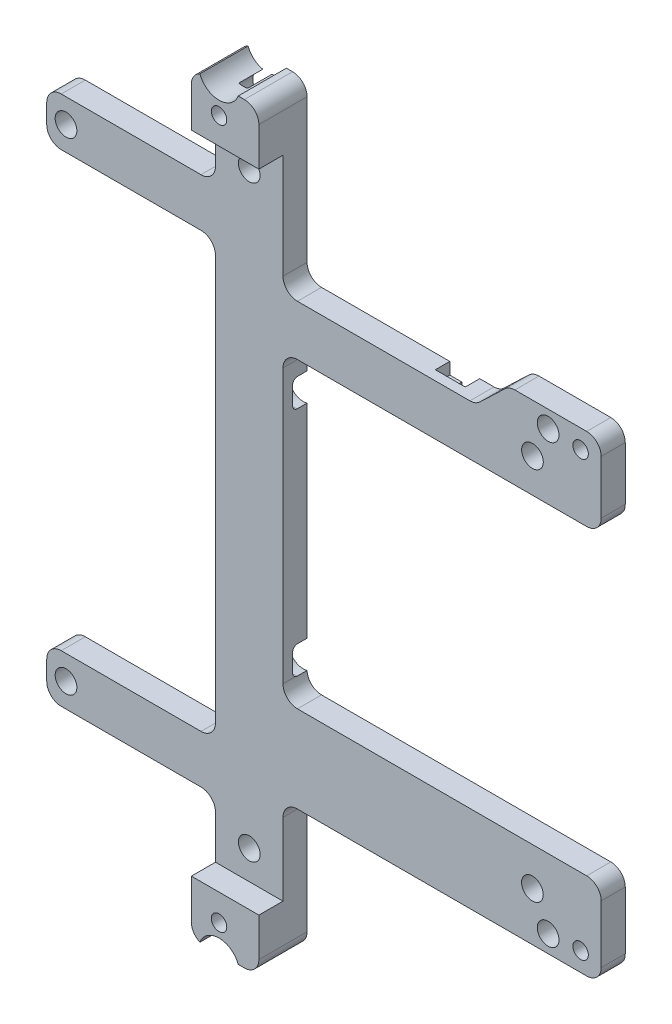
SolidWorks part; units mm, degrees
ref_plane "Front Plane" through (0, 0, 0) normal (1, 0, 0) x (0, 1, 0)
ref_plane "Top Plane" through (0, 0, 0) normal (0, 0, 1) x (0, 1, 0)
ref_plane "Right Plane" through (0, 0, 0) normal (0, 1, 0) x (-1, 0, 0)
sketch "Sketch1" plane through (0, 0, 0) normal (0, 0, 1) x (0, 1, 0)
  line L0 (-38.86, 0.005) -> (38.86, -0.005) construction
  line L1 (-38.86, 0.005) -> (38.86, -0.005) construction
  line L2 (0, 0) -> (0, 106.5364) construction
  line L13 (-67.5, 65.745) -> (67.5, 51.745) construction
  line L14 (-67.5, 51.745) -> (67.5, 65.745) construction
  line L17 (-45, 65.745) -> (45, 65.745)
  line L22 (62.0223, 59.9423) -> (59.9389, 57.5466) construction
  line L23 (62.1784, 57.7039) -> (59.7816, 59.7861) construction
  line L45 (42.2651, 11.7705) -> (42.2651, 52.7631) construction
  line L47 (-48.9476, 51.745) -> (-48.9476, -14.255)
  line L48 (-48.9476, -14.255) -> (-30.9476, -14.255)
  line L49 (-30.9476, -14.255) -> (-30.9476, 51.745)
  line L50 (-30.9476, 51.745) -> (31.792, 51.745)
  line L51 (31.792, 51.745) -> (31.792, -14.255)
  line L52 (31.792, -14.255) -> (48.8866, -14.255)
  line L53 (48.8866, -14.255) -> (48.8866, 4.8443)
  line L54 (48.8866, 4.8443) -> (42.2651, 11.7705)
  line L55 (42.2651, 11.7705) -> (42.2651, 51.745)
  line L60 (-55, 65.745) -> (-78, 65.745)
  line L62 (-78, 65.745) -> (-78, 51.745)
  line L63 (-78, 51.745) -> (-48.9476, 51.745)
  line L64 (78, 65.745) -> (78, 51.745)
  line L65 (55, 65.745) -> (78, 65.745)
  line L66 (78, 51.745) -> (42.2651, 51.745)
  line L67 (-55, 65.745) -> (-55, 100.745)
  line L68 (-55, 100.745) -> (-45, 100.745)
  line L69 (-45, 100.745) -> (-45, 65.745)
  line L70 (45, 100.745) -> (45, 65.745)
  line L71 (55, 100.745) -> (45, 100.745)
  line L72 (55, 65.745) -> (55, 100.745)
  circle A0 centre (-38.86, 0.005) radius 2.25
  circle A1 centre (38.86, -0.005) radius 2.25
  circle A2 centre (-60.99, 58.735) radius 2.25
  circle A3 centre (60.98, 58.745) radius 2.25
  circle A8 centre (-45, -9.995) radius 1.6
  circle A10 centre (45, -9.995) radius 1.6
  circle A14 centre (60.98, 58.745) radius 1.5874 construction
  circle A15 centre (-72.5, 60.005) radius 3
  circle A17 centre (72.5, 60.005) radius 3
  point P28 (0, 58.745)
  dimension "D1" = 4.5
  dimension "D4" = 4.5
  dimension "D5" = 4.5
  dimension "D10" = 4.5
  dimension "D11" = 3.2
  dimension "D13" = 45
  dimension "D12" = 10
  dimension "D14" = 6
  dimension "D16" = 70
  dimension "D2" = 77.72
  dimension "D3" = 0.01
  dimension "D6" = 22.13
  dimension "D7" = 58.73
  dimension "D8" = 99.84
  dimension "D9" = 58.74
  dimension "D15" = 72.5
  dimension "D17" = 14
  dimension "D18" = 23
  dimension "D19" = 10
  dimension "D20" = 35
  dimension "D22" = 66
  dimension "D23" = 18
  dimension "D24" = 62.7397
extrude "Boss-Extrude1" add sketch "Sketch1" along normal blind 5
sketch "Sketch4" plane through (0, 0, 5) normal (0, 0, 1) x (1, 0, 0)
  line L0 (-59.9423, 62.0223) -> (-57.5466, 59.9389) construction
  line L1 (-57.7039, 62.1784) -> (-59.7861, 59.7816) construction
  line L2 (-52.7631, 68.2675) -> (-66.1639, 68.2675) construction
  line L3 (-66.1639, 68.2675) -> (-66.1639, 50.4408) construction
  line L4 (-66.1639, 50.4408) -> (-106.6121, 50.4408) construction
  line L5 (-106.6121, 50.4408) -> (-106.6121, 34.0894) construction
  line L6 (-106.6121, 34.0894) -> (-66.1639, 34.0894) construction
  line L7 (-66.1639, 34.0894) -> (-66.1639, -39.7992) construction
  line L8 (-66.1639, -39.7992) -> (-105.8744, -39.7992) construction
  line L9 (-105.8744, -39.7992) -> (-105.8744, -55.1671) construction
  line L10 (-105.8744, -55.1671) -> (-65.4262, -55.1671) construction
  line L11 (-65.4262, -55.1671) -> (-65.4262, -83.2031) construction
  line L12 (-65.4262, -83.2031) -> (-51.2429, -83.2031) construction
  line L13 (-51.2429, -83.2031) -> (-51.2429, -48.9476) construction
  line L14 (-51.2429, -48.9476) -> (16.9144, -48.9476) construction
  line L15 (16.9144, -48.9476) -> (16.9144, -14.8647) construction
  line L16 (16.9144, -14.8647) -> (-49.6702, -14.8647) construction
  line L17 (-49.6702, -14.8647) -> (-49.6702, 30.0022) construction
  line L18 (-49.6702, 30.0022) -> (-49.6702, 31.792) construction
  line L19 (-49.6702, 31.792) -> (21.8605, 31.792) construction
  line L20 (21.8605, 31.792) -> (21.8605, 50.4408) construction
  line L21 (21.8605, 50.4408) -> (-3.2186, 50.4408) construction
  line L22 (-3.2186, 50.4408) -> (-11.7705, 42.2651) construction
  line L23 (-11.7705, 42.2651) -> (-52.7631, 42.2651) construction
  line L24 (-52.7631, 42.2651) -> (-52.7631, 68.2675) construction
  line L25 (-53.5293, 13.6559) -> (-53.5293, 8.5989) construction
  line L26 (-53.5293, 13.6559) -> (-57.5472, 13.6559) construction
  line L27 (-57.5472, 13.6559) -> (-57.5472, 8.5989) construction
  line L28 (-53.5293, 8.5989) -> (-57.5472, 8.5989) construction
  line L29 (-53.5293, 13.6559) -> (-57.5472, 8.5989) construction
  line L30 (-57.5472, 13.6559) -> (-53.5293, 8.5989) construction
  line L31 (-30.5241, 33.1453) -> (-30.5241, 30.4388) construction
  line L32 (-30.5241, 33.1453) -> (-34.3522, 33.1453) construction
  line L33 (-34.3522, 33.1453) -> (-34.3522, 30.4388) construction
  line L34 (-30.5241, 30.4388) -> (-34.3522, 30.4388) construction
  line L35 (-30.5241, 33.1453) -> (-34.3522, 30.4388) construction
  line L36 (-34.3522, 33.1453) -> (-30.5241, 30.4388) construction
  line L37 (-34.5262, 33.1453) -> (-34.5262, 30.4388) construction
  line L38 (-34.5262, 33.1453) -> (-37.7452, 33.1453) construction
  line L39 (-37.7452, 33.1453) -> (-37.7452, 30.4388) construction
  line L40 (-34.5262, 30.4388) -> (-37.7452, 30.4388) construction
  line L41 (-34.5262, 33.1453) -> (-37.7452, 30.4388) construction
  line L42 (-37.7452, 33.1453) -> (-34.5262, 30.4388) construction
  line L43 (-16.3911, 40.3217) -> (-16.3911, 37.7641) construction
  line L44 (-16.3911, 40.3217) -> (-19.6245, 40.3217) construction
  line L45 (-19.6245, 40.3217) -> (-19.6245, 37.7641) construction
  line L46 (-16.3911, 37.7641) -> (-19.6245, 37.7641) construction
  line L47 (-16.3911, 40.3217) -> (-19.6245, 37.7641) construction
  line L48 (-19.6245, 40.3217) -> (-16.3911, 37.7641) construction
  line L49 (-15.9373, 44.8094) -> (-15.9373, 40.9494) construction
  line L50 (-15.9373, 44.8094) -> (-22.1441, 44.8094) construction
  line L51 (-22.1441, 44.8094) -> (-22.1441, 40.9494) construction
  line L52 (-15.9373, 40.9494) -> (-22.1441, 40.9494) construction
  line L53 (-15.9373, 44.8094) -> (-22.1441, 40.9494) construction
  line L54 (-22.1441, 44.8094) -> (-15.9373, 40.9494) construction
  circle A0 centre (-58.745, 60.98) radius 1.5874 construction
  circle A1 centre (-52.5383, 22.8611) radius 3 construction
  circle A2 centre (-52.5383, -25.1544) radius 3 construction
  circle A3 centre (-10.615, -39.3884) radius 1 construction
  circle A4 centre (-10.615, -46.9884) radius 1 construction
  circle A5 centre (-19.6245, -25.1544) radius 3 construction
  circle A6 centre (-58.745, 60.98) radius 2.25 construction
  point P33 (-55.5383, 11.1274)
  point P44 (-32.4381, 31.792)
  point P49 (-36.1357, 31.792)
  point P54 (-18.0078, 39.0429)
  point P59 (-19.0407, 42.8794)
sketch "Sketch5" plane through (0, 0, 0) normal (0, 0, -1) x (1, 0, 0)
  line L0 (-16.3911, -39.8089) -> (-15.9373, -39.8089)
  line L1 (-57.5472, -8.5989) -> (-53.5293, -8.5989)
  line L2 (-57.5472, -8.5989) -> (-57.5472, -13.6559)
  line L3 (-57.5472, -13.6559) -> (-53.5293, -13.6559)
  line L4 (-53.5293, -8.5989) -> (-53.5293, -13.6559)
  line L5 (-57.5472, -8.5989) -> (-53.5293, -13.6559) construction
  line L6 (-57.5472, -13.6559) -> (-53.5293, -8.5989) construction
  line L7 (-37.7452, -30.4388) -> (-30.5241, -30.4388)
  line L8 (-37.7452, -30.4388) -> (-37.7452, -33.1453)
  line L9 (-37.7452, -33.1453) -> (-30.5241, -33.1453)
  line L10 (-30.5241, -30.4388) -> (-30.5241, -33.1453)
  line L11 (-19.6245, -37.7641) -> (-16.3911, -37.7641)
  line L12 (-19.6245, -37.7641) -> (-19.6245, -39.8089)
  line L14 (-16.3911, -37.7641) -> (-16.3911, -39.8089)
  line L15 (-22.1441, -39.8089) -> (-19.6245, -39.8089)
  line L16 (-22.1441, -39.8089) -> (-22.1441, -44.8094)
  line L17 (-22.1441, -44.8094) -> (-15.9373, -44.8094)
  line L18 (-15.9373, -39.8089) -> (-15.9373, -44.8094)
  circle A0 centre (-52.5383, -22.8611) radius 3
  circle A1 centre (-52.5383, 25.1544) radius 3
  circle A2 centre (-10.615, 46.9884) radius 1
  circle A3 centre (-10.615, 39.3884) radius 1
  point P6 (-55.5383, -11.1274)
extrude "Cut-Extrude1" cut sketch "Sketch5" against normal blind 3
sketch "Sketch7" plane through (0, 0, 5) normal (0, 0, 1) x (1, 0, 0)
  line L0 (-51.745, 42.2651) -> (-51.745, 78) construction
  line L1 (-65.745, 78) -> (-51.745, 78)
  line L2 (-65.745, 78) -> (-65.745, 67)
  line L3 (-65.745, 67) -> (-51.745, 67)
  line L4 (-51.745, 78) -> (-51.745, 67)
  line L5 (0, 0) -> (-129.6565, 0) construction
  line L6 (-51.745, -78) -> (-51.745, -67)
  line L7 (-65.745, -67) -> (-51.745, -67)
  line L8 (-65.745, -78) -> (-65.745, -67)
  line L9 (-65.745, -78) -> (-51.745, -78)
  dimension "D1" = 11
extrude "Boss-Extrude2" add sketch "Sketch7" along normal blind 5
sketch "Sketch8" plane through (0, 0, 10) normal (0, 0, 1) x (1, 0, 0)
  line L0 (0, 0) -> (-41.2457, 0) construction
  circle A0 centre (-60.005, 72.5) radius 1.6
  circle A1 centre (-60.005, -72.5) radius 1.6
  dimension "D1" = 3.2
extrude "Cut-Extrude2" cut sketch "Sketch8" against normal blind 10
fillet "Fillet2" radius 1 15 edges at (-11.615, -46.9884, 3) (-11.615, -39.3884, 3) (-18.0078, 37.7641, 3) (-16.3911, 38.7865, 3) (-19.6245, 38.7865, 3) (-20.8843, 39.8089, 3) (-30.5241, 32.4687, 3) (-37.7452, 32.4687, 3) (-34.1347, 33.1453, 3) (-55.5383, 22.8611, 3) (-55.5383, -25.1544, 3) (-55.5383, 8.5989, 3) (-53.5293, 11.1274, 3) (-55.5383, 13.6559, 3) (-57.5472, 11.1274, 3)
sketch "Sketch9" plane through (0, 0, 10) normal (0, 0, 1) x (1, 0, 0)
  line L0 (0, 0) -> (-47.8889, 0) construction
  circle A0 centre (-60.005, 79.5) radius 4.25
  circle A2 centre (-60.005, -79.5) radius 4.25
extrude "Cut-Extrude3" cut sketch "Sketch9" against normal blind 10
sketch "Sketch10" plane through (0, 0, 0) normal (0, 0, -1) x (1, 0, 0)
  circle A0 centre (9.995, 45) radius 3
  circle A1 centre (9.995, -45) radius 3
  dimension "D1" = 6
  dimension "D2" = 6
extrude "Cut-Extrude4" cut sketch "Sketch10" against normal blind 2
fillet "Fillet1" radius 3 22 edges at (-51.745, -78, 5) (-65.745, -78, 5) (-65.745, -55, 2.5) (-100.745, -55, 2.5) (-100.745, -45, 2.5) (-65.745, -45, 2.5) (-65.745, 45, 2.5) (-100.745, 45, 2.5) (-100.745, 55, 2.5) (-65.745, 55, 2.5) (-65.745, 78, 5) (-51.745, 78, 5) (-51.745, 42.2651, 2.5) (-11.7705, 42.2651, 2.5) (-4.8443, 48.8866, 2.5) (14.255, 48.8866, 2.5) (14.255, 31.792, 2.5) (-51.745, 31.792, 2.5) (-51.745, -30.9476, 2.5) (14.255, -30.9476, 2.5) (14.255, -48.9476, 2.5) (-51.745, -48.9476, 2.5)
sketch "Sketch11" plane through (0, 0, 5) normal (0, 0, 1) x (1, 0, 0)
  line L0 (-68.745, -45) -> (-97.745, -45) construction
  line L1 (-100.745, -48) -> (-100.745, -52) construction
  line L2 (0, 0) -> (-111.0274, 0) construction
  line L3 (-48.745, -48.9476) -> (11.255, -48.9476) construction
  line L4 (14.255, -45.9476) -> (14.255, -33.9476) construction
  circle A0 centre (-96.745, -50) radius 2.25
  circle A1 centre (-96.745, 50) radius 2.25
  circle A2 centre (3.255, -45.3476) radius 2.25
  circle A5 centre (3.255, 45.3476) radius 2.25
  dimension "D1" = 4.5
  dimension "D4" = 4.5
  dimension "D2" = 5
  dimension "D3" = 4
  dimension "D5" = 3.6
  dimension "D6" = 11
extrude "Cut-Extrude5" cut sketch "Sketch11" against normal blind 10
